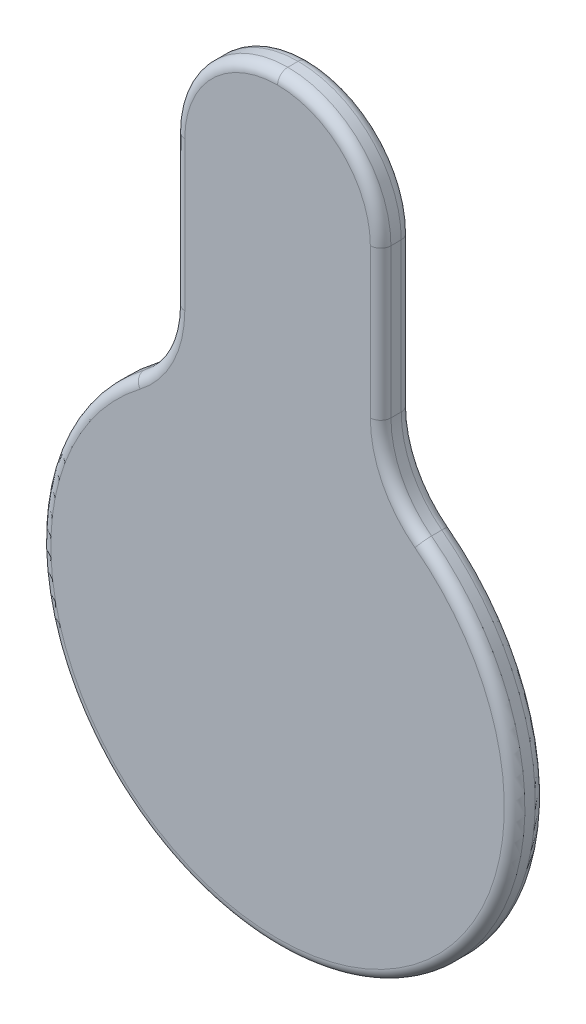
SolidWorks part; units mm, degrees
ref_plane "Front Plane" through (0, 0, 0) normal (0, 0, 1) x (1, 0, 0)
ref_plane "Top Plane" through (0, 0, 0) normal (0, 1, 0) x (1, 0, 0)
ref_plane "Right Plane" through (0, 0, 0) normal (1, 0, 0) x (0, 0, -1)
sketch "Sketch1" plane through (0, 0, 0) normal (0, 0, 1) x (1, 0, 0)
  line L1 (25.4, 128.8093) -> (-25.4, 128.8093)
  line L2 (25.4, 128.8093) -> (25.4, 52.6093)
  line L4 (-25.4, 128.8093) -> (-25.4, 52.6093)
  circle A0 centre (0, 0) radius 58.42
  point P7 (0, 0)
  point P8 (0, 0)
  point P9 (0, 0)
  point P10 (-25.4, 52.6093)
  dimension "D1" = 116.84
  dimension "D2" = 76.2
  dimension "D3" = 50.8
extrude "Boss-Extrude1" add sketch "Sketch1" along normal blind 7.62 contours A0 | A0 L2 L1 L4 region at (0, 92.6459, 0) region at (0, 0, 0)
fillet "Fillet1" radius 25.4 2 edges at (-25.4, 128.8093, 3.81) (25.4, 128.8093, 3.81)
fillet "Fillet2" radius 25.4 2 edges at (25.4, 52.6093, 3.81) (-25.4, 52.6093, 3.81)
fillet "Fillet3" radius 2.54 14 edges at (-28.0386, 55.3991, 0) (-25.4, 85.0406, 0) (-17.9605, 121.3698, 0) (17.9605, 121.3698, 0) (25.4, 85.0406, 0) (28.0386, 55.3991, 0) (-28.0386, 55.3991, 7.62) (-25.4, 85.0406, 7.62) (-17.9605, 121.3698, 7.62) (17.9605, 121.3698, 7.62) (25.4, 85.0406, 7.62) (28.0386, 55.3991, 7.62) (0, -58.42, 0) (0, -58.42, 7.62)
